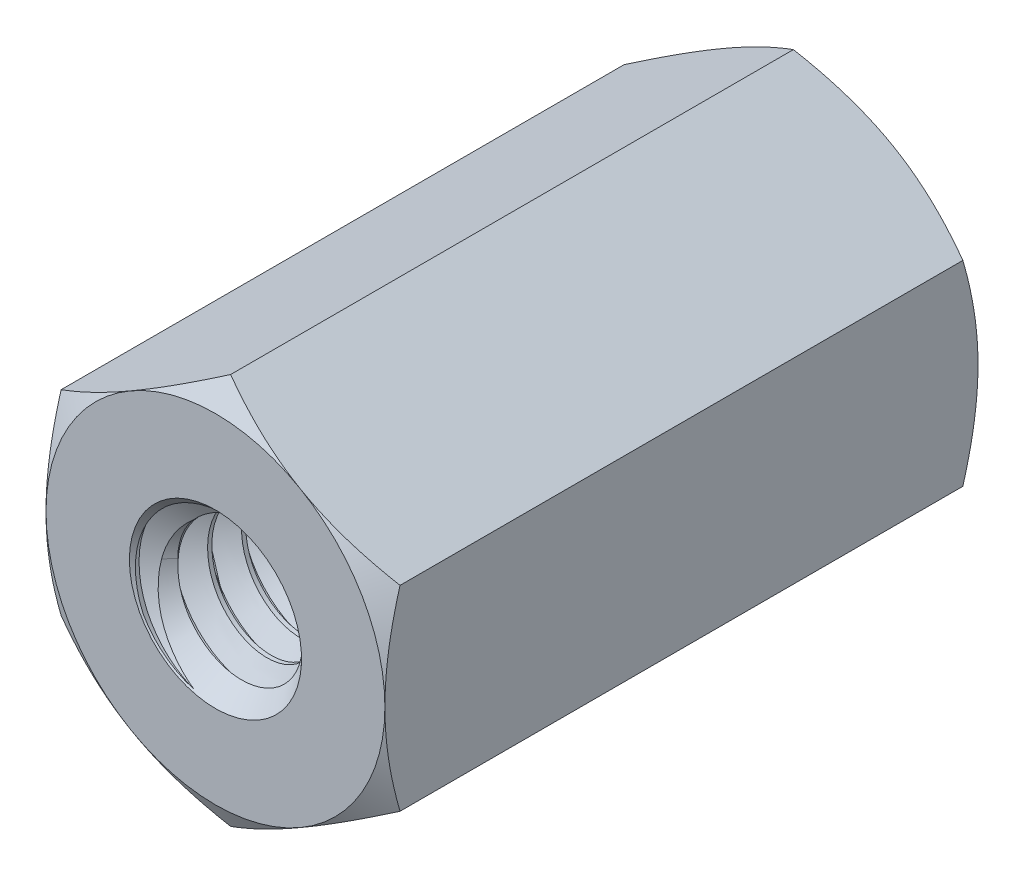
SolidWorks part; units mm, degrees
ref_plane "Front Plane" through (0, 0, 0) normal (0, 0, 1) x (1, 0, 0)
ref_plane "Top Plane" through (0, 0, 0) normal (0, 1, 0) x (1, 0, 0)
ref_plane "Right Plane" through (0, 0, 0) normal (1, 0, 0) x (0, 0, -1)
sketch "Sketch3" plane through (0, 0, 0) normal (1, 0, 0) x (0, 0, -1)
  line L0 (-11.1125, 0) -> (11.1125, 0) construction
  line L1 (0, 6.35) -> (0, -6.35) construction
  line L2 (-11.1125, 3.175) -> (-11.1125, -3.175) construction
  point P2 (-4.7625, 0)
  point P3 (4.7625, 0)
  dimension "Length" = 22.225
  dimension "Min Thread Length" = 15.875
  dimension "D1" = 15.875
  dimension "Thread Dia" = 6.35
  dimension "Hex" = 12.7
sketch "Sketch1" plane through (0, 0, 0) normal (0, 0, 1) x (1, 0, 0)
  line L1 (0, 7.3323) -> (-6.35, 3.6662)
  line L2 (-6.35, 3.6662) -> (-6.35, -3.6662)
  line L3 (-6.35, -3.6662) -> (0, -7.3323)
  line L4 (0, -7.3323) -> (6.35, -3.6662)
  line L5 (6.35, -3.6662) -> (6.35, 3.6662)
  line L6 (6.35, 3.6662) -> (0, 7.3323)
  circle A0 centre (0, 0) radius 6.35 construction
  circle A1 centre (0, 0) radius 3.175
extrude "Extrude1" add sketch "Sketch1" along normal up to vertex (11.1125 mm away) and the other way up to vertex (11.1125 mm away) up to point (0, 0, 11.1125) other way up to point (0, 0, -11.1125)
sketch "Sketch11" plane through (0, 0, -11.1125) normal (0, 0, -1) x (-1, 0, 0)
  circle A0 centre (0, 0) radius 3.175 construction
  circle A1 centre (0, 0) radius 3.175
curve "Helix/Spiral1" pitch 1.27 height 23.495 radius 3.175 centre (0, 0, -11.1125) axis (0, 0, 1) start towards (0, 1, 0) parameters "Pitch"=1.27
sketch "Sketch12" plane through (0, 0, 0) normal (1, 0, 0) x (0, 0, -1)
  line L0 (12.2238, 3.175) -> (11.1125, 3.175)
  line L1 (12.2238, 3.175) -> (11.7475, 2.3501)
  line L2 (11.7475, 2.3501) -> (11.5888, 2.3501)
  line L3 (11.5888, 2.3501) -> (11.1125, 3.175)
  line L4 (11.6681, 2.3501) -> (11.6681, 3.175) construction
  line L5 (11.9856, 2.7626) -> (11.3506, 2.7626) construction
  dimension "D1" = 0.1588
  dimension "D2" = 0.635
  dimension "D3" = 60
sweep "Sweep1" add profiles "Sketch12" path "Helix/Spiral1"
sketch "Sketch6" plane through (0, 0, -11.1125) normal (0, 0, -1) x (-1, 0, 0)
  line L6 (0, 7.3323) -> (-6.35, 3.6662)
  line L7 (-6.35, 3.6662) -> (-6.35, -3.6662)
  line L8 (-6.35, -3.6662) -> (0, -7.3323)
  line L9 (0, -7.3323) -> (6.35, -3.6662)
  line L10 (6.35, -3.6662) -> (6.35, 3.6662)
  line L11 (6.35, 3.6662) -> (0, 7.3323)
  line L12 (0, 7.3323) -> (-6.35, 3.6662)
  line L13 (-6.35, 3.6662) -> (-6.35, -3.6662)
  line L14 (-6.35, -3.6662) -> (0, -7.3323)
  line L15 (0, -7.3323) -> (6.35, -3.6662)
  line L16 (6.35, -3.6662) -> (6.35, 3.6662)
  line L17 (6.35, 3.6662) -> (0, 7.3323)
  dimension "D1" = 0
extrude "Extrude2" cut sketch "Sketch6" along normal through all
sketch "Sketch7" plane through (0, 0, -11.1125) normal (0, 0, -1) x (-1, 0, 0)
  circle A2 centre (0, 0) radius 3.2258
  circle A3 centre (0, 0) radius 3.2258
  dimension "D1" = 0.0508
extrude "Extrude3" cut sketch "Sketch7" against normal through all draft 43
sketch "Sketch8" plane through (0, 0, -11.1125) normal (0, 0, -1) x (-1, 0, 0)
  circle A0 centre (0, 0) radius 6.35 construction
  circle A1 centre (0, 0) radius 6.35
extrude "Extrude4" cut sketch "Sketch8" against normal through all draft 60 flip side to cut
mirror "Mirror1" about plane through (0, 0, 0) normal (0, 0, 1) of "Extrude2", "Extrude3", "Extrude4"
sketch "Sketch9" [suppressed] plane through (0, 0, 0) normal (1, 0, 0) x (0, 0, -1)
  line L1 (-22.225, 3.2258) -> (22.225, 3.2258)
  line L2 (-22.225, 3.2258) -> (-22.225, 0)
  line L3 (-22.225, 0) -> (22.225, 0)
  line L4 (22.225, 3.2258) -> (22.225, 0)
  line L7 (-38.1, 0) -> (38.1, 0) construction
revolve "Revolve" [suppressed] add sketch "Sketch9" angle 360 about L0
sketch "Sketch10" [suppressed] plane through (0, 0, 0) normal (1, 0, 0) x (0, 0, -1)
  line L0 (38.1, 3.175) -> (22.225, 3.175)
  line L1 (-38.1, 3.175) -> (-22.225, 3.175)
  line L2 (22.225, 3.175) -> (22.225, -3.175)
  line L3 (-38.1, -3.2258) -> (-22.225, -3.2258)
  line L4 (-22.225, 3.175) -> (-22.225, -3.2258)
  line L5 (22.225, -3.175) -> (38.1, -3.175)
equation "\"D1@Sketch3\" = \"Min Thread Length@Sketch3\""
equation "\"D3@Helix/Spiral1\" = \"Length@Sketch3\"+\"Pitch@Helix/Spiral1\""
equation "\"D1@Sketch12\" = \"Pitch@Helix/Spiral1\"*.125"
equation "\"D2@Sketch12\" = \"Pitch@Helix/Spiral1\"*.5"
